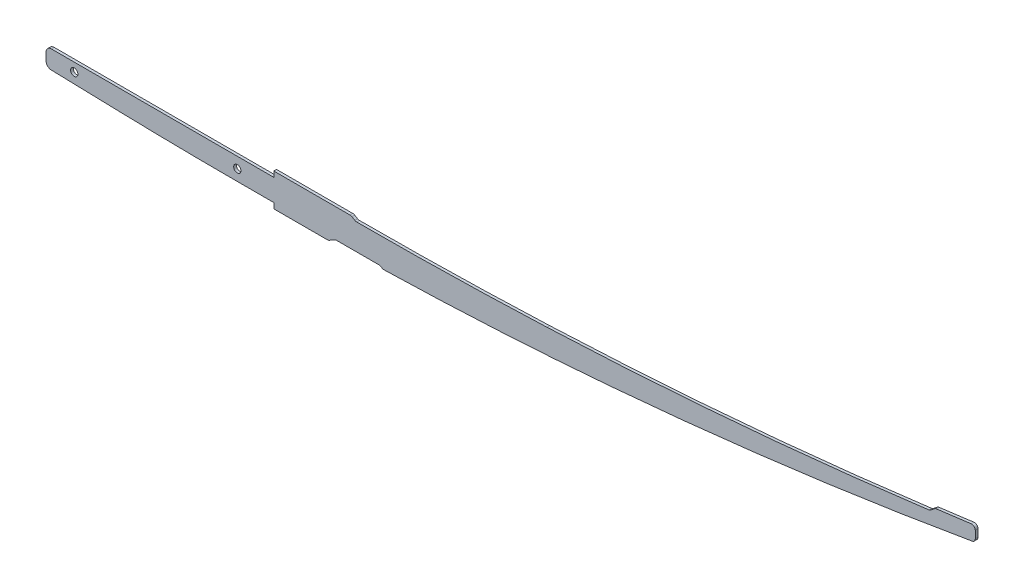
SolidWorks part; units mm, degrees
ref_plane "前视基准面" through (0, 0, 0) normal (0, 0, 1) x (1, 0, 0)
ref_plane "上视基准面" through (0, 0, 0) normal (0, 1, 0) x (1, 0, 0)
ref_plane "右视基准面" through (0, 0, 0) normal (1, 0, 0) x (0, 0, -1)
sketch "草图1" plane through (0, 0, 0) normal (0, 0, 1) x (1, 0, 0)
  line L0 (0, 81.9069) -> (0, 12) construction
  line L1 (0, 18) -> (84.8038, 18)
  line L2 (84.8038, 18) -> (90, 15)
  line L3 (0, -18) -> (60, -18)
  line L4 (60, -18) -> (67.7942, -13.5)
  line L5 (67.7942, -13.5) -> (116.5359, -13.5)
  line L6 (116.5359, -13.5) -> (120, -15.5)
  line L7 (0, 18) -> (0, 12)
  line L8 (-48.3677, 0) -> (26.6044, 0) construction
  line L9 (720, 55.4943) -> (726.3011, 60.3141)
  line L10 (726.3011, 60.3141) -> (770, 66)
  line L11 (770, 66) -> (770, 50)
  line L12 (90, 15) -> (0, 15) construction
  line L13 (720, 55.4943) -> (770, 62) construction
  line L14 (120, -15.5) -> (0, -15.5) construction
  line L15 (120, -15.5) -> (0, -18.5) construction
  line L16 (0, 12) -> (-244, 12)
  line L17 (0, -12) -> (-40, -12)
  line L18 (-170, -10.2071) -> (-244.1655, -8.161)
  line L19 (-250, 6) -> (-250, -2.1632)
  line L21 (0, -12) -> (0, -18)
  line L22 (0, 12) -> (0, 0) construction
  line L23 (0, -12) -> (0, -75.7106) construction
  arc A0 (90, 15) -> (300, 19.4119) centre (90, 5015) ccw
  arc A1 (120, -15.5) -> (370, -1.7848) centre (15.0328, 4183.1881) ccw
  arc A2 (300, 19.4119) -> (720, 55.4943) centre (97.3037, 4841.2569) ccw
  arc A3 (370, -1.7848) -> (770, 50) centre (-16.363, 4553.3361) ccw
  arc A4 (0, 0) -> (-279, 4) centre (0, 9732.125) cw construction
  arc A5 (-40, -12) -> (-170, -10.2071) centre (-40, 4701.8911) cw
  arc A6 (-244.1655, -8.161) -> (-250, -2.1632) centre (-244, -2.1632) cw
  arc A7 (-244, 12) -> (-250, 6) centre (-244, 6) ccw
  circle A8 centre (-40, 0.0822) radius 4.01
  circle A9 centre (-219, 2.4644) radius 4.01
  point P39 (-250, -8)
  dimension "D1" = 770
  dimension "D3" = 300
  dimension "D16" = 50
  dimension "D17" = 50
  dimension "D19" = 5000
  dimension "D20" = 4200
  dimension "D22" = 4
  dimension "D24" = 40
  dimension "D29" = 6
  dimension "D30" = 8.02
  dimension "D32" = 8.02
  dimension "D2" = 36
  dimension "D4" = 400
  dimension "D5" = 30
  dimension "D6" = 30
  dimension "D7" = 30
  dimension "D8" = 30
  dimension "D9" = 16
  dimension "D10" = 120
  dimension "D11" = 90
  dimension "D12" = 3
  dimension "D13" = 5
  dimension "D14" = 2
  dimension "D15" = 60
  dimension "D18" = 12
  dimension "D21" = 3
  dimension "D23" = 279
  dimension "D25" = 250
  dimension "D26" = 80
  dimension "D27" = 4
  dimension "D28" = 24
  dimension "D31" = 40
  dimension "D33" = 60
extrude "凸台-拉伸1" add sketch "草图1" along normal mid plane 3 contours L16 A7 L19 A6 L18 A5 L17 L7 | A1 A3 L11 L10 L9 A2 A0 L2 L1 L7 L3 L4 L5 L6 region at (225.6908, 10.4129, 0)
fillet "圆角1" radius 4 2 edges at (770, 66, 0) (770, 50, 0)
fillet "圆角3" radius 4 8 edges at (720, 55.4943, 0) (726.3011, 60.3141, 0) (90, 15, 0) (84.8038, 18, 0) (120, -15.5, 0) (116.5359, -13.5, 0) (67.7942, -13.5, 0) (60, -18, 0)
